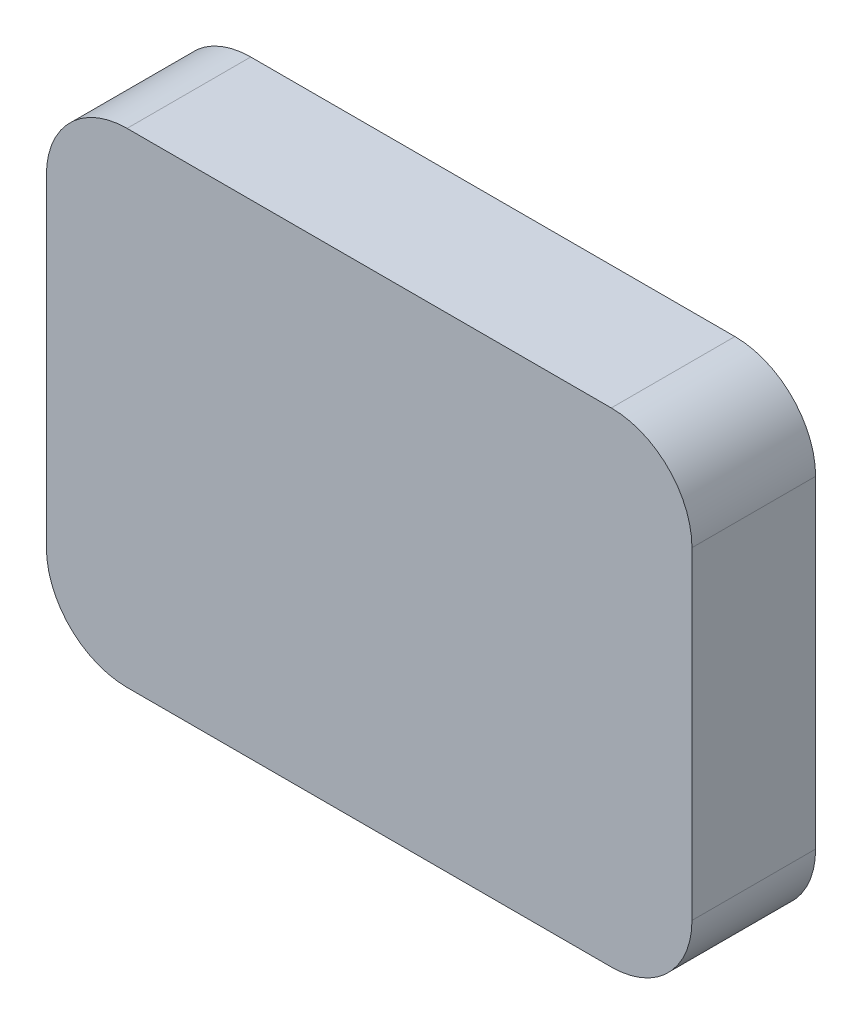
SolidWorks part; units mm, degrees
ref_plane "Plan de face" through (0, 0, 0) normal (0, 0, 1) x (1, 0, 0)
ref_plane "Plan de dessus" through (0, 0, 0) normal (0, 1, 0) x (1, 0, 0)
ref_plane "Plan de droite" through (0, 0, 0) normal (1, 0, 0) x (0, 0, -1)
sketch "Esquisse1" plane through (0, 0, 0) normal (0, 0, 1) x (1, 0, 0)
  line L1 (-30, 30) -> (30, 30)
  line L2 (-40, 20) -> (-40, -20)
  line L3 (-30, -30) -> (30, -30)
  line L4 (40, 20) -> (40, -20)
  line L5 (-40, 30) -> (40, -30) construction
  line L6 (-40, -30) -> (40, 30) construction
  arc A0 (-40, -20) -> (-30, -30) centre (-30, -20) ccw
  arc A1 (30, -30) -> (40, -20) centre (30, -20) ccw
  arc A2 (30, 30) -> (40, 20) centre (30, 20) cw
  arc A3 (-30, 30) -> (-40, 20) centre (-30, 20) ccw
  point P0 (0, 0)
  dimension "D1" = 10
  dimension "D2" = 60
  dimension "D3" = 40
sketch "profil" plane through (0, 0, 0) normal (1, 0, 0) x (0, 0, -1)
  line L0 (0, -28.4) -> (4.1391, -28.4)
  line L1 (4.1391, -28.4) -> (14.1228, -23.8)
  line L3 (14.1228, -30) -> (0, -30)
  line L4 (0, -30) -> (0, -28.4)
  line L6 (0, -20) -> (0, -30) construction
  line L7 (0, -30) -> (0, 30) construction
  line L8 (14.1228, -23.8) -> (14.1228, -25.4)
  line L9 (14.1228, -28.4) -> (14.1228, -30)
  arc A1 (14.1228, -25.4) -> (14.1228, -28.4) centre (14.1228, -26.9) cw
  dimension "D1" = 3
  dimension "D2" = 1.6
  dimension "D3" = 14.1228
sweep "Balayage1" add profiles "profil" path "Esquisse1"
extrude "Boss.-Extru.1" add sketch "Esquisse1<3>" along normal blind 1.2
sketch "Esquisse1<3>" plane through (0, 0, 0) normal (0, 0, 1) x (1, 0, 0) same geometry as "Esquisse1"
fillet "Congé1" radius 2 9 edges at (-35.9397, 25.9397, 0) (-38.4, 0, 0) (-35.9397, -25.9397, 0) (-15, -28.4, 0) (15, -28.4, 0) (35.9397, -25.9397, 0) (38.4, 0, 0) (35.9397, 25.9397, 0) (0, 28.4, 0)
equation "\"buse\"=0.4"
equation "\"coque\"= \"buse\" * 4"
equation "\"diam_silicone\"=3"
equation "\"D1@profil\" = \"diam_silicone\""
equation "\"couche\"=0.2"
equation "\"D1@Boss.-Extru.1\"=\"fond\""
equation "\"fond\"= \"couche\" * 6"
equation "\"D2@Esquisse1\"=\"dim_ext_L@boitier_balaye-1.Part\""
equation "\"D3@profil\"=\"hauteur_boitier@boitier_balaye-1.Part\""
